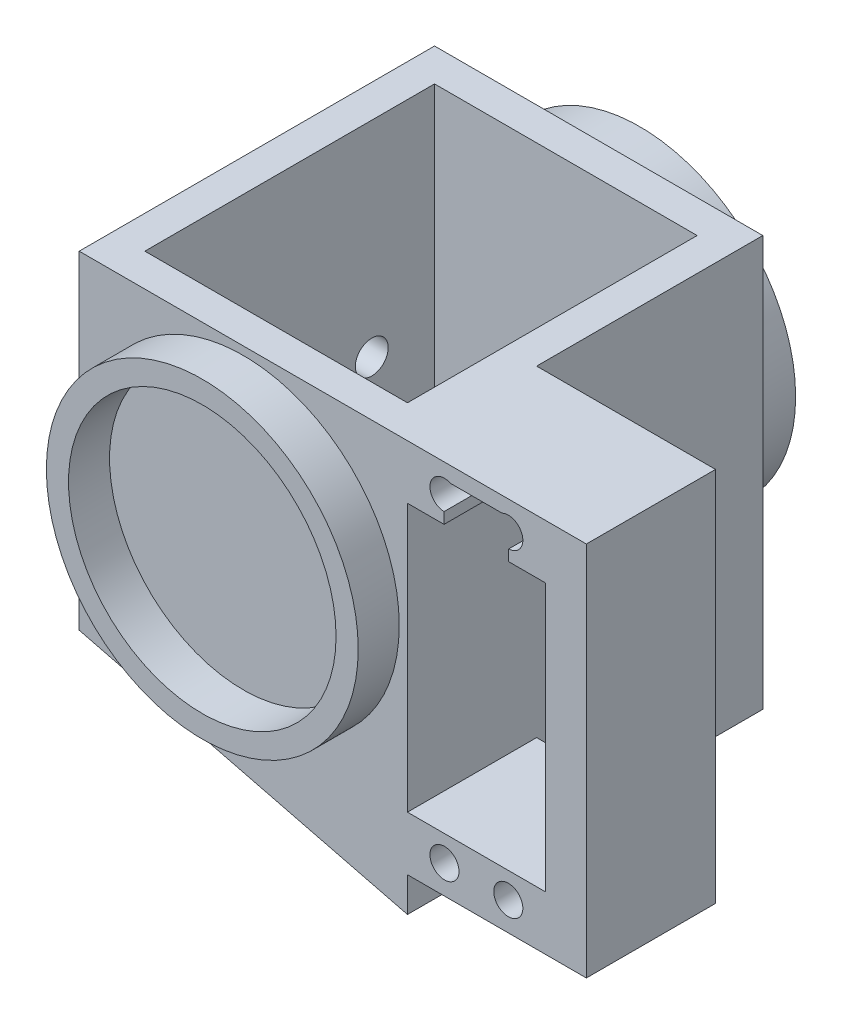
SolidWorks part; units mm, degrees
ref_plane "Front Plane" through (0, 0, 0) normal (0, 0, 1) x (1, 0, 0)
ref_plane "Top Plane" through (0, 0, 0) normal (0, 1, 0) x (1, 0, 0)
ref_plane "Right Plane" through (0, 0, 0) normal (1, 0, 0) x (0, 0, -1)
sketch "Sketch1" plane through (0, 0, 0) normal (0, 0, 1) x (1, 0, 0)
  line L1 (-25.4, 25.4) -> (25.4, 25.4)
  line L2 (-25.4, 25.4) -> (-25.4, -25.4)
  line L3 (-25.4, -25.4) -> (25.4, -25.4)
  line L4 (25.4, 25.4) -> (25.4, -25.4)
  point P4 (0, 25.4)
  point P6 (25.4, 0)
  dimension "D1" = 50.8
  dimension "D2" = 50.8
extrude "Boss-Extrude1" add sketch "Sketch1" along normal up to surface (54.991 mm away) contours L4 L3 L2 L1
sketch "Sketch7" plane through (0, 0, 54.991) normal (0, 0, 1) x (1, 0, 0)
  line L0 (25.4, -25.4) -> (25.4, -38.1)
  line L1 (25.4, -38.1) -> (-25.4, -25.4)
  line L2 (-25.4, -25.4) -> (25.4, -25.4)
  dimension "D1" = 12.7
extrude "Boss-Extrude3" add sketch "Sketch7" against normal up to surface (54.991 mm away) up to face at (0, 0, 0)
sketch "Sketch2" plane through (0, 25.4, 0) normal (0, 1, 0) x (1, 0, 0)
  line L8 (-20.32, -49.911) -> (20.32, -49.911)
  line L9 (20.32, -49.911) -> (20.32, -5.08)
  line L10 (20.32, -5.08) -> (-20.32, -5.08)
  line L11 (-20.32, -5.08) -> (-20.32, -49.911)
  line L12 (-20.32, -49.911) -> (20.32, -49.911)
  line L13 (20.32, -49.911) -> (20.32, -5.08)
  line L14 (20.32, -5.08) -> (-20.32, -5.08)
  line L15 (-20.32, -5.08) -> (-20.32, -49.911)
  dimension "D1" = 5.08
extrude "Cut-Extrude1" cut sketch "Sketch2" against normal through all
sketch "Sketch3" plane through (0, 0, 54.991) normal (0, 0, 1) x (1, 0, 0)
  circle A0 centre (0, 0) radius 20.701
  circle A1 centre (0, 0) radius 24.13
  dimension "D1" = 41.402
  dimension "D2" = 48.26
extrude "Boss-Extrude2" add sketch "Sketch3" along normal blind 6.35
ref_plane "Plane1" through (0, 0, 27.4955) normal (0, 0, 1) x (1, 0, 0)
mirror "Mirror1" about plane through (0, 0, 27.4955) normal (0, 0, 1) of "Boss-Extrude2"
sketch "Sketch4" plane through (-25.4, 0, 0) normal (-1, 0, 0) x (0, 0, 1)
  line L0 (0, 25.4) -> (54.991, 25.4) construction
  line L1 (54.991, 25.4) -> (0, 25.4) construction
  line L2 (0, 25.4) -> (0, -25.4) construction
  line L3 (54.991, -25.4) -> (54.991, 25.4) construction
  line L4 (27.4955, 25.4) -> (27.4955, 2.664) construction
  line L5 (14.7955, -6.35) -> (40.1955, -6.35) construction
  circle A0 centre (14.7955, -6.35) radius 2.54
  circle A1 centre (40.1955, -6.35) radius 2.54
  point P14 (27.4955, -6.35)
  dimension "D1" = 5.08
  dimension "D2" = 5.08
  dimension "D3" = 25.4
  dimension "D4" = 31.75
extrude "Cut-Extrude2" cut sketch "Sketch4" against normal up to next
sketch "Sketch6" plane through (25.4, 0, 0) normal (1, 0, 0) x (0, 0, -1)
  line L0 (-54.991, 25.4) -> (0, 25.4) construction
  line L1 (-54.991, 25.4) -> (-35.0012, 25.4)
  line L2 (-54.991, 25.4) -> (-54.991, 17.018)
  line L3 (-54.991, 17.018) -> (-35.0012, 17.018)
  line L4 (-35.0012, 25.4) -> (-35.0012, 17.018)
  line L5 (-54.991, -38.1) -> (-54.991, 25.4) construction
  line L6 (-54.991, -3.683) -> (-26.7766, -3.683) construction
  line L7 (-54.991, -32.766) -> (-54.991, -24.384)
  line L8 (-54.991, -32.766) -> (-35.0012, -32.766)
  line L9 (-35.0012, -32.766) -> (-35.0012, -24.384)
  line L10 (-54.991, -24.384) -> (-35.0012, -24.384)
  dimension "D1" = 8.382
  dimension "D2" = 19.9898
  dimension "D3" = 41.402
extrude "Boss-Extrude4" add sketch "Sketch6" along normal blind 21.336
sketch "Sketch8" plane through (46.736, 0, 0) normal (1, 0, 0) x (0, 0, -1)
  line L1 (-54.991, 25.4) -> (-35.0012, 25.4)
  line L2 (-54.991, 25.4) -> (-54.991, -32.766)
  line L3 (-54.991, -32.766) -> (-35.0012, -32.766)
  line L4 (-35.0012, 25.4) -> (-35.0012, -32.766)
extrude "Boss-Extrude5" add sketch "Sketch8" along normal blind 6.35
sketch "Sketch9" plane through (0, 0, 54.991) normal (0, 0, 1) x (1, 0, 0)
  line L0 (46.736, 17.018) -> (25.4, 17.018) construction
  line L1 (36.068, 17.018) -> (36.068, 27.3381) construction
  line L2 (46.736, -3.683) -> (30.2152, -3.683) construction
  line L3 (46.736, 17.018) -> (46.736, -24.384) construction
  line L4 (36.068, -24.384) -> (36.068, -34.7041) construction
  line L5 (31.0642, 17.018) -> (31.0642, 18.7334)
  line L6 (32.089, 23.0124) -> (40.047, 23.0124)
  line L7 (41.0718, 18.7334) -> (41.0718, 17.018)
  line L8 (31.0642, 17.018) -> (41.0718, 17.018)
  arc A0 (41.0718, 18.7334) -> (40.047, 23.0124) centre (41.0083, 20.9804) ccw
  arc A1 (32.089, 23.0124) -> (31.0642, 18.7334) centre (31.1277, 20.9804) ccw
  circle A2 centre (31.1277, -28.3464) radius 2.2479
  circle A3 centre (41.0083, -28.3464) radius 2.2479
  dimension "D7" = 4.4958
  dimension "D8" = 4.4958
  dimension "D1" = 3.9624
  dimension "D2" = 9.8806
  dimension "D3" = 9.8806
  dimension "D4" = 10.0076
  dimension "D5" = 10.0076
  dimension "D6" = 5.9944
extrude "Cut-Extrude3" cut sketch "Sketch9" against normal through all
